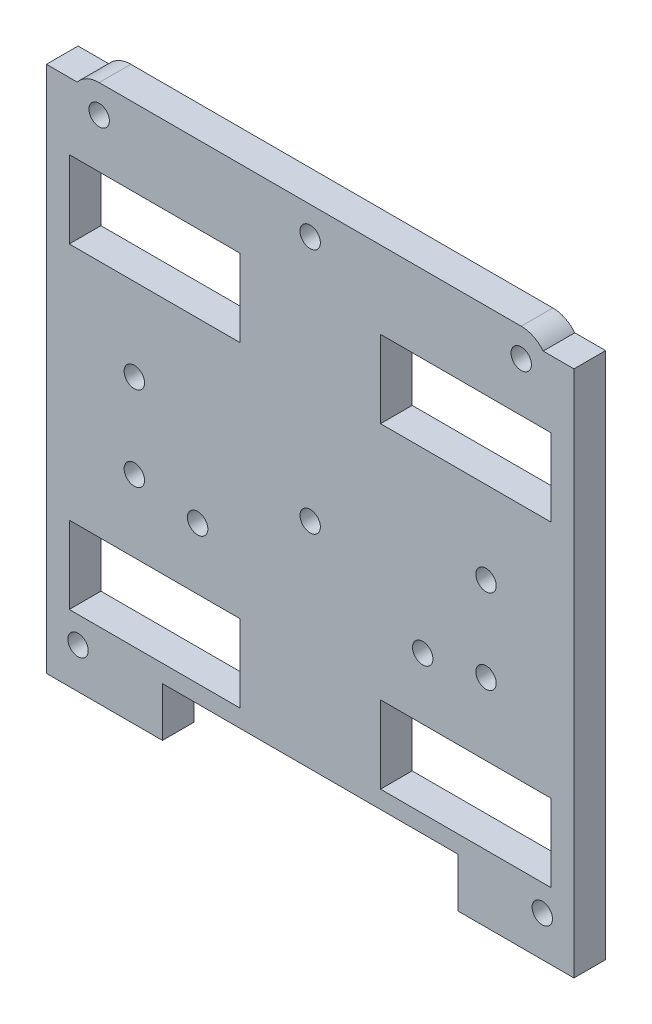
SolidWorks part; units mm, degrees
ref_plane "Front Plane" through (0, 0, 0) normal (0, 0, 1) x (1, 0, 0)
ref_plane "Top Plane" through (0, 0, 0) normal (0, 1, 0) x (1, 0, 0)
ref_plane "Right Plane" through (0, 0, 0) normal (1, 0, 0) x (0, 0, -1)
sketch "Sketch1" plane through (0, 0, 0) normal (0, 0, 1) x (1, 0, 0)
  line L0 (0, -37.5) -> (0, 37.5) construction
  line L1 (-47.5, -37.5) -> (47.5, -37.5)
  line L2 (-47.5, -37.5) -> (-47.5, 37.5)
  line L3 (-47.5, 37.5) -> (47.5, 37.5)
  line L4 (47.5, -37.5) -> (47.5, 37.5)
  line L5 (-47.5, -37.5) -> (47.5, 37.5) construction
  line L6 (-47.5, 37.5) -> (47.5, -37.5) construction
  line L7 (-47.5, 0) -> (47.5, 0) construction
  line L8 (-47.5, 22.5) -> (47.5, 22.5) construction
  line L9 (34.25, 17) -> (10, 28) construction
  line L10 (-34.25, 28) -> (-10, 28)
  line L11 (-34.25, 28) -> (-34.25, 17)
  line L12 (-34.25, 17) -> (-10, 17)
  line L13 (-10, 28) -> (-10, 17)
  line L14 (-34.25, 28) -> (-10, 17) construction
  line L15 (-34.25, 17) -> (-10, 28) construction
  line L16 (34.25, 28) -> (10, 17) construction
  line L17 (10, 28) -> (10, 17)
  line L18 (34.25, 17) -> (10, 17)
  line L19 (34.25, 28) -> (34.25, 17)
  line L20 (34.25, 28) -> (10, 28)
  line L21 (34.25, -28) -> (10, -17) construction
  line L22 (-34.25, -17) -> (-10, -28) construction
  line L23 (-34.25, -28) -> (-10, -17) construction
  line L24 (34.25, -17) -> (10, -28) construction
  line L25 (34.25, -28) -> (10, -28)
  line L26 (34.25, -28) -> (34.25, -17)
  line L27 (34.25, -17) -> (10, -17)
  line L28 (10, -28) -> (10, -17)
  line L29 (-10, -28) -> (-10, -17)
  line L30 (-34.25, -17) -> (-10, -17)
  line L31 (-34.25, -28) -> (-34.25, -17)
  line L32 (-34.25, -28) -> (-10, -28)
  point P0 (0, 0)
  point P12 (-22.125, 22.5)
  point P21 (22.125, 22.5)
  point P30 (22.125, -22.5)
  point P31 (-22.125, -22.5)
  dimension "D1" = 95
  dimension "D2" = 75
  dimension "D3" = 22.5
  dimension "D4" = 24.25
  dimension "D5" = 11
  dimension "D6" = 10
extrude "Boss-Extrude1" add sketch "Sketch1" along normal blind 4.5
sketch "Sketch8" plane through (0, 0, 4.5) normal (0, 0, 1) x (1, 0, 0)
  line L0 (-47.5, 37.5) -> (-47.5, -37.5) construction
  line L1 (47.5, -37.5) -> (47.5, 37.5) construction
  circle A0 centre (-47.5, 29.5) radius 8
  circle A1 centre (47.5, 29.5) radius 8
  dimension "D1" = 16
extrude "Boss-Extrude2" [suppressed] add sketch "Sketch8" against normal through all
sketch "Sketch2" plane through (0, 0, 4.5) normal (0, 0, 1) x (1, 0, 0)
  line L0 (0, -37.5) -> (0, 37.5) construction
  line L1 (-47.5, -37.5) -> (47.5, -37.5) construction
  line L2 (47.5, 37.5) -> (-47.5, 37.5) construction
  line L3 (-47.5, 0) -> (47.5, 0) construction
  line L4 (-47.5, 37.5) -> (-47.5, -37.5) construction
  line L5 (47.5, -37.5) -> (47.5, 37.5) construction
  line L6 (-40, 0) -> (40, 0) construction
  line L7 (-30, 35) -> (30, 35) construction
  circle A0 centre (-30, 35) radius 1.45
  circle A1 centre (30, 35) radius 1.45
  circle A2 centre (40, 0) radius 1.45
  circle A3 centre (-40, 0) radius 1.45
  circle A4 centre (0, 35) radius 1.45
  dimension "D1" = 2.9
  dimension "D7" = 2.9
  dimension "D8" = 2.9
  dimension "D9" = 2.9
  dimension "D2" = 30
  dimension "D3" = 35
  dimension "D4" = 80
  dimension "D5" = 40
  dimension "D6" = 0
extrude "screwHoles" cut sketch "Sketch2" against normal through all
sketch "Sketch3" plane through (0, 0, 4.5) normal (0, 0, 1) x (1, 0, 0)
  line L0 (-47.5, -20) -> (26.0486, -20) construction
  line L1 (-47.5, 37.5) -> (-47.5, -37.5) construction
  line L3 (0, 37.5) -> (0, -37.5) construction
  line L4 (47.5, 37.5) -> (-47.5, 37.5) construction
  line L5 (-47.5, -37.5) -> (47.5, -37.5) construction
  line L6 (18.95, -22.2) -> (9.05, -17.8) construction
  line L7 (-18.95, -17.8) -> (-9.05, -17.8)
  line L8 (-18.95, -17.8) -> (-18.95, -22.2)
  line L9 (-18.95, -22.2) -> (-9.05, -22.2)
  line L10 (-9.05, -17.8) -> (-9.05, -22.2)
  line L11 (-18.95, -17.8) -> (-9.05, -22.2) construction
  line L12 (-18.95, -22.2) -> (-9.05, -17.8) construction
  line L13 (18.95, -17.8) -> (9.05, -22.2) construction
  line L14 (9.05, -17.8) -> (9.05, -22.2)
  line L15 (18.95, -22.2) -> (9.05, -22.2)
  line L16 (18.95, -17.8) -> (18.95, -22.2)
  line L17 (18.95, -17.8) -> (9.05, -17.8)
  line L18 (-47.5, 37.5) -> (-47.5, -37.5) construction
  point P2 (-47.5, 0)
  point P12 (-14, -20)
  point P21 (14, -20)
  dimension "D1" = 9.9
  dimension "D3" = 14
  dimension "D4" = 20
extrude "BeltClamp" [suppressed] cut sketch "Sketch3" against normal through all
sketch "Sketch4" plane through (0, 0, 4.5) normal (0, 0, 1) x (1, 0, 0)
  line L0 (-47.5, 0) -> (47.5, 0) construction
  line L1 (-47.5, 37.5) -> (-47.5, -37.5) construction
  line L2 (47.5, -37.5) -> (47.5, 37.5) construction
  line L3 (0, 0) -> (0, 33.55) construction
  line L4 (-29.85, 2.175) -> (-20.15, 2.175)
  line L5 (-29.85, 2.175) -> (-29.85, -2.175)
  line L6 (-29.85, -2.175) -> (-20.15, -2.175)
  line L7 (-20.15, 2.175) -> (-20.15, -2.175)
  line L8 (-29.85, 2.175) -> (-20.15, -2.175) construction
  line L9 (-29.85, -2.175) -> (-20.15, 2.175) construction
  line L10 (29.85, -2.175) -> (20.15, 2.175) construction
  line L11 (29.85, 2.175) -> (20.15, -2.175) construction
  line L12 (20.15, 2.175) -> (20.15, -2.175)
  line L13 (29.85, -2.175) -> (20.15, -2.175)
  line L14 (29.85, 2.175) -> (29.85, -2.175)
  line L15 (29.85, 2.175) -> (20.15, 2.175)
  line L16 (-29.85, -2.175) -> (-20.15, 2.175) construction
  circle A0 centre (-40, 0) radius 1.45 construction
  circle A1 centre (0, 35) radius 1.45 construction
  circle A2 centre (0, 0) radius 1.45
  point P6 (-25, 0)
  point P22 (25, 0)
  dimension "D5" = 2.9
  dimension "D3" = 0
  dimension "D2" = 4.35
  dimension "D4" = 25
extrude "Cut-Extrude3" cut sketch "Sketch4" against normal through all
sketch "Sketch5" plane through (0, 0, 4.5) normal (0, 0, 1) x (1, 0, 0)
  line L0 (-47.5, -9.75) -> (47.5, -9.75) construction
  line L1 (-47.5, 37.5) -> (-47.5, -37.5) construction
  line L2 (47.5, -37.5) -> (47.5, 37.5) construction
  line L4 (0, -37.5) -> (0, 37.5) construction
  line L5 (-47.5, -37.5) -> (47.5, -37.5) construction
  line L6 (47.5, 37.5) -> (-47.5, 37.5) construction
  line L7 (-30.825, -14.6) -> (-35.175, -4.9) construction
  line L8 (30.825, -4.9) -> (35.175, -4.9)
  line L9 (30.825, -4.9) -> (30.825, -14.6)
  line L10 (30.825, -14.6) -> (35.175, -14.6)
  line L11 (35.175, -4.9) -> (35.175, -14.6)
  line L12 (30.825, -4.9) -> (35.175, -14.6) construction
  line L13 (30.825, -14.6) -> (35.175, -4.9) construction
  line L14 (-30.825, -4.9) -> (-35.175, -14.6) construction
  line L15 (-35.175, -4.9) -> (-35.175, -14.6)
  line L16 (-30.825, -14.6) -> (-35.175, -14.6)
  line L17 (-30.825, -4.9) -> (-30.825, -14.6)
  line L18 (-30.825, -4.9) -> (-35.175, -4.9)
  line L19 (33, -9.75) -> (33, -37.5) construction
  line L20 (-33, -9.75) -> (-33, -37.5) construction
  line L21 (-33, -31.75) -> (33, -31.75) construction
  circle A0 centre (33, -31.75) radius 1.45
  circle A1 centre (-33, -31.75) radius 1.45
  point P15 (33, -9.75)
  point P24 (-33, -9.75)
  dimension "D5" = 2.9
  dimension "D2" = 9.7
  dimension "D3" = 4.35
  dimension "D4" = 33
  dimension "D6" = 22
  dimension "D1" = 9.75
extrude "Cut-Extrude4" cut sketch "Sketch5" against normal through all
sketch "Sketch9" plane through (0, 0, 4.5) normal (0, 0, 1) x (1, 0, 0)
  line L0 (47.5, 37.5) -> (-47.5, 37.5) construction
  line L1 (0, 37.5) -> (0, -37.5) construction
  line L2 (-47.5, -37.5) -> (47.5, -37.5) construction
  line L3 (50.5, 35) -> (45.5, 35) construction
  line L4 (-50.5, 35) -> (-45.5, 35) construction
  circle A0 centre (-30, 35) radius 4
  circle A1 centre (-30, 35) radius 1.45
  circle A2 centre (-30, 35) radius 1.45 construction
  circle A3 centre (30, 35) radius 1.45
  circle A4 centre (30, 35) radius 4
  point P17 (0, -37.5)
  dimension "D1" = 8
extrude "Boss-Extrude3" add sketch "Sketch9" against normal through all
sketch "Sketch10" plane through (0, 0, 4.5) normal (0, 0, 1) x (1, 0, 0)
  line L0 (-60, 37.5) -> (-37.5, 37.5)
  line L1 (-37.5, 37.5) -> (-37.5, -37.5)
  line L2 (-47.5, -37.5) -> (47.5, -37.5) construction
  line L3 (-37.5, -37.5) -> (-60, -37.5)
  line L4 (-60, -37.5) -> (-60, 37.5)
  line L5 (0, 37.5) -> (0, -37.5) construction
  line L6 (26.8775, 37.5) -> (-26.8775, 37.5) construction
  line L7 (60, -37.5) -> (60, 37.5)
  line L8 (37.5, -37.5) -> (60, -37.5)
  line L9 (37.5, 37.5) -> (37.5, -37.5)
  line L10 (60, 37.5) -> (37.5, 37.5)
  line L11 (-60, -37.5) -> (-60, 37.5)
  line L12 (-33.1225, 37.5) -> (-47.5, 37.5) construction
  line M3 (47.5, -37.5) -> (47.5, 37.5)
  line M7 (-47.5, 37.5) -> (-47.5, -37.5)
  line M8 (-47.5, -37.5) -> (47.5, -37.5)
  dimension "D3" = 0
  dimension "D1" = 75
  dimension "D2" = 60
extrude "Cut-Extrude5" cut sketch "Sketch10" against normal through all contours L1 L0 M7 M8 | L10 L9 M3 M8 region at (42.5, 0, 4.5) region at (-42.5, 0, 4.5)
sketch "Sketch11" plane through (0, 0, 4.5) normal (0, 0, 1) x (1, 0, 0)
  line L0 (-30, 39) -> (30, 39)
  line L1 (30, 39) -> (26.8775, 37.5)
  line L2 (26.8775, 37.5) -> (-26.8775, 37.5)
  line L3 (-26.8775, 37.5) -> (-30, 39)
  arc A0 (-26.8775, 37.5) -> (-33.1225, 37.5) centre (-30, 35) ccw construction
  arc A1 (33.1225, 37.5) -> (26.8775, 37.5) centre (30, 35) ccw construction
extrude "Boss-Extrude4" add sketch "Sketch11" against normal through all
sketch "Sketch12" plane through (0, 0, 4.5) normal (0, 0, 1) x (1, 0, 0)
  line L0 (-37.5, -8.25) -> (37.5, -8.25) construction
  line L1 (-37.5, 37.5) -> (-37.5, -37.5) construction
  line L2 (37.5, 37.5) -> (37.5, -37.5) construction
  line L3 (0, 0) -> (0, -37.5) construction
  line L4 (-37.5, -37.5) -> (37.5, -37.5) construction
  circle A0 centre (-16, -8.25) radius 1.45
  circle A1 centre (16, -8.25) radius 1.45
  dimension "D2" = 2.9
  dimension "D1" = 16
  dimension "D3" = 8.25
extrude "FanBraceScrews" cut sketch "Sketch12" against normal through all
sketch "Sketch13" plane through (0, 0, 4.5) normal (0, 0, 1) x (1, 0, 0)
  line L0 (-37.5, -37.5) -> (37.5, -37.5) construction
  line L1 (-21, -44.5) -> (21, -44.5)
  line L2 (-21, -44.5) -> (-21, -30.5)
  line L3 (-21, -30.5) -> (21, -30.5)
  line L4 (21, -44.5) -> (21, -30.5)
  line L5 (-21, -44.5) -> (21, -30.5) construction
  line L6 (-21, -30.5) -> (21, -44.5) construction
  point P0 (0, -37.5)
  dimension "D1" = 42
  dimension "D2" = 7
extrude "Cut-Extrude7" cut sketch "Sketch13" against normal through all
sketch "Sketch14" plane through (0, 0, 4.5) normal (0, 0, 1) x (1, 0, 0)
  line L0 (16, -9.7) -> (16, 3.75) construction
  line L1 (0, 0) -> (0, -40.3958) construction
  line L2 (-16, -9.7) -> (-16, 3.75) construction
  circle A0 centre (16, -8.25) radius 1.45 construction
  circle A1 centre (16, 3.75) radius 1.45
  circle A2 centre (-16, 3.75) radius 1.45
  dimension "D2" = 2.9
  dimension "D1" = 12
extrude "Cut-Extrude8" [suppressed] cut sketch "Sketch14" against normal through all
sketch "Sketch15" plane through (0, 0, 4.5) normal (0, 0, 1) x (1, 0, 0)
  line L0 (-25, 5.25) -> (-25, -6.75) construction
  line L2 (0, 0) -> (0, -11.0705) construction
  line L3 (16, -8.3509) -> (25, -6.75) construction
  line L4 (25, 5.25) -> (25, -6.75) construction
  circle A0 centre (-25, 5.25) radius 1.45
  circle A1 centre (-25, -6.75) radius 1.45
  circle A2 centre (25, -6.75) radius 1.45
  circle A3 centre (25, 5.25) radius 1.45
  circle A5 centre (-16, -8.25) radius 1.45 construction
  dimension "D1" = 12
  dimension "D3" = 2.9
  dimension "D4" = 2.9
  dimension "D2" = 25
  dimension "D5" = 1.5
extrude "BeltClipScrews" cut sketch "Sketch15" against normal through all
sketch "Sketch16" plane through (0, 0, 4.5) normal (0, 0, 1) x (1, 0, 0)
  line L0 (0, 0) -> (0, -11.3016) construction
  line L1 (-29.85, 2.175) -> (-20.15, 2.175)
  line L2 (-29.85, 2.175) -> (-29.85, -2.175)
  line L3 (-29.85, -2.175) -> (-20.15, -2.175)
  line L4 (-20.15, 2.175) -> (-20.15, -2.175)
  line L5 (-35.175, -4.9) -> (-30.825, -4.9)
  line L6 (-35.175, -4.9) -> (-35.175, -14.6)
  line L7 (-35.175, -14.6) -> (-30.825, -14.6)
  line L8 (-30.825, -4.9) -> (-30.825, -14.6)
  line L9 (30.825, -4.9) -> (30.825, -14.6)
  line L10 (35.175, -14.6) -> (30.825, -14.6)
  line L11 (35.175, -4.9) -> (35.175, -14.6)
  line L12 (35.175, -4.9) -> (30.825, -4.9)
  line L13 (20.15, 2.175) -> (20.15, -2.175)
  line L14 (29.85, -2.175) -> (20.15, -2.175)
  line L15 (29.85, 2.175) -> (29.85, -2.175)
  line L16 (29.85, 2.175) -> (20.15, 2.175)
  line L17 (-30.825, -4.9) -> (-30.825, -14.6)
extrude "Boss-Extrude5" add sketch "Sketch16" against normal through all contours L8 L5 L6 L7 | L4 L1 L2 L3 | L15 L16 L13 L14 | L11 L12 L9 L10 region at (-25, 0, 4.5) region at (-33, -9.75, 4.5) region at (33, -9.75, 4.5) region at (25, 0, 4.5)
equation "\"X-ROD-SPACING\"=45"
equation "\"Y-ROD-SPACING\"=75"
equation "\"Z-ROD-SPACING\"=17.5"
equation "\"Y-BED-OFFSET\"=2"
equation "\"Y-BED-ROD-INSET\"=3.5"
equation "\"Y-BED-SCREW-SPACING\"=209"
equation "\"Y-BED-SCREW-CUTOUT-SLOT-HEIGHT\"=2"
equation "\"T-SLOT-NUT-FILLET-RADIUS\"=0.5"
equation "\"T-SLOT-SCREW-SHAFT-RADIUS\"=1.55"
equation "\"T-SLOT-SCREW-SHAFT-CUTOUT-LENGTH\"=11"
equation "\"T-SLOT-NUT-DEPTH\"=3.5"
equation "\"T-SLOT-NUT-WIDTH\"=2.85"
equation "\"T-SLOT-NUT-END-DISTANCE\"=8"
equation "\"ACRYLIC-THICKNESS\"=10"
equation "\"ACRYLIC-THICKNESS2\"=4.5"
equation "\"ACRYLIC-TAB-CUTOUT-SIZE\"=\"ACRYLIC-THICKNESS\"+\"ACRYLIC-TAB-TOLERANCE\"*2"
equation "\"ACRYLIC-TAB-WIDTH\"=\"ACRYLIC-THICKNESS\""
equation "\"ACRYLIC-M3-HOLE\"=2.9"
equation "\"SMOOTHROD-CAP-SCREW-DISTANCE\"=20"
equation "\"FRAME-WIDTH-INNER\"=370"
equation "\"NEMA17-HOLE-SPACING\"=31"
equation "\"NEMA17-CENTRAL-CUTOUT\"=22.5"
equation "\"Z-BRACKET-REACH\"=55"
equation "\"Z-ROD-INSET\"=13.5"
equation "\"TOP-BRACKET-SPACING\"=40"
equation "\"SMOOTHROD-X-LENGTH\"=350"
equation "\"SMOOTHROD-Y-LENGTH\"=350"
equation "\"SMOOTHROD-Z-LENGTH\"=350"
equation "\"SMOOTHROD-TIGHTENING-HEADROOM\"=.25"
equation "\"LEADSCREW-Z-LENGTH\"=300"
equation "\"SCREW-LENGTH-FRAME\"=\"ACRYLIC-THICKNESS\" + 10"
equation "\"SCREW-LENGTH-MOTOR\"=\"ACRYLIC-THICKNESS\" + 5"
equation "\"SCREW-HEAD-RADIUS\"=6"
equation "\"PRINTED-X-SMOOTHROD-DIAMETER\"=8.8"
equation "\"PRINTED-X-SMOOTHROD-CUTOUT\"=10"
equation "\"PRINTED-X-BASE-HEIGHT\"=10"
equation "\"PRINTED-LM8UU-CUTOUT-SIZE\"=15.5"
equation "\"PRINTED-LM8UU-CUTOUT-LENGTH\"=24.5"
equation "\"PRINTED-X-IDLER-HEIGHT\"=16"
equation "\"PSU-MOUNTING-WIDTH\"=95"
equation "\"PSU-MOUNTING-HEIGHT\"=177"
equation "\"Y-BELT-TO-ROD-DISTANCE\"=20"
equation "\"SPOOL-HOLDER-ROD-SPACING\"=150"
equation "\"D3@Sketch1\"=\"X-ROD-SPACING\"/2"
equation "\"D4@Sketch1\"=\"ACRYLIC-X-CARRIAGE-LM8UU-CUTOUT-WIDTH\""
equation "\"D1@Boss-Extrude1\"=\"ACRYLIC-THICKNESS2\""
equation "\"D1@Sketch2\"=\"ACRYLIC-M3-HOLE\""
equation "\"D1@Sketch3\"=\"ACRYLIC-TAB-CUTOUT-SIZE\""
equation "\"D2@Sketch3\"=\"ACRYLIC-THICKNESS2\"+\"ACRYLIC-TAB-TOLERANCE\"*2"
equation "\"ACRYLIC-X-CARRIAGE-WIDTH\"=55"
equation "\"ACRYLIC-X-CARRIAGE-HEIGHT\"=75"
equation "\"D2@Sketch1\"=\"ACRYLIC-X-CARRIAGE-HEIGHT\""
equation "\"ACRYLIC-X-CARRIAGE-CENTER-TAB-SPACING\"=14"
equation "\"D3@Sketch3\"=\"ACRYLIC-X-CARRIAGE-CENTER-TAB-SPACING\""
equation "\"SCREW-LENGTH-EXTRUDER\"=28"
equation "\"ACRYLIC-X-CARRIAGE-SCREW-SPACING-X\"=15"
equation "\"ACRYLIC-X-CARRIAGE-SCREW-SPACING-Y\"=33"
equation "\"D1@Sketch4\"=\"ACRYLIC-TAB-WIDTH\"-\"KERF\"*4"
equation "\"D2@Sketch4\"=\"ACRYLIC-THICKNESS2\"-\"KERF\"*2"
equation "\"D2@Sketch5\"=\"ACRYLIC-TAB-WIDTH\"-\"KERF\"*4"
equation "\"D3@Sketch5\"=\"ACRYLIC-THICKNESS2\"-\"KERF\"*2"
equation "\"ACRYLIC-X-CARRIAGE-EXTRUDER-SHELF-DEPTH\"=\"ACRYLIC-X-CARRIAGE-EXTRUDER-OFFSET\" + 28"
equation "\"ACRYLIC-X-CARRIAGE-EXTRUDER-BRACE-SPACING\"=23"
equation "\"D4@Sketch5\"=\"ACRYLIC-X-CARRIAGE-DUAL-MOUNT-BRACE-WIDTH\""
equation "\"D1@Sketch5\"=\"ACRYLIC-THICKNESS2\"/2 + 7.5"
equation "\"D4@Sketch2\"=\"ACRYLIC-X-CARRIAGE-DUAL-MOUNT-SCREW-WIDTH\"*2"
equation "\"D5@Sketch2\"=\"ACRYLIC-X-CARRIAGE-DUAL-MOUNT-SCREW-WIDTH\""
equation "\"D7@Sketch2\"=\"ACRYLIC-M3-HOLE\""
equation "\"D8@Sketch2\"=\"ACRYLIC-M3-HOLE\""
equation "\"ACRYLIC-X-CARRIAGE-LM8UU-CUTOUT-WIDTH\"=24.25"
equation "\"ACRYLIC-TAB-TOLERANCE\"=-.05"
equation "\"ACRYLIC-X-CARRIAGE-EXTRUDER-OFFSET\"=26"
equation "\"ACRYLIC-X-CARRIAGE-EXTRUDER-ANGLE\"=90"
equation "\"ACRYLIC-X-CARRIAGE-EXTRUDER-BRACE-TAB-OFFSET\"=20"
equation "\"ACRYLIC-X-CARRIAGE-EXTRUDER-BRACE-HEIGHT\"=35"
equation "\"ACRYLIC-X-CARRIAGE-EXTRUDER-BRACE-SCREW-SPACING\"=22"
equation "\"D5@Sketch5\"=\"ACRYLIC-M3-HOLE\""
equation "\"ACRYLIC-X-CARRIAGE-DUAL-WIDTH-MULTIPLIER\"=1.65"
equation "\"ACRYLIC-X-CARRIAGE-DUAL-HOTEND-SPACING\"=42"
equation "\"ACRYLIC-X-CARRIAGE-DUAL-WIDTH\"=75"
equation "\"ACRYLIC-X-CARRIAGE-DUAL-HOTEND-SEPARATION\"=36"
equation "\"ACRYLIC-X-CARRIAGE-DUAL-MOUNT-PLATE-DEPTH\"=75"
equation "\"ACRYLIC-X-CARRIAGE-DUAL-MOUNT-BRACE-WIDTH\"=33"
equation "\"ACRYLIC-X-CARRIAGE-DUAL-MOUNT-SCREW-WIDTH\"=40"
equation "\"D9@Sketch2\"=\"ACRYLIC-M3-HOLE\""
equation "\"ACRYLIC-X-CARRIAGE-LM8UU-CUTOUT-HEIGHT\"=11.0"
equation "\"D5@Sketch1\"=\"ACRYLIC-X-CARRIAGE-LM8UU-CUTOUT-HEIGHT\""
equation "\"D1@Sketch10\"=\"ACRYLIC-X-CARRIAGE-DUAL-WIDTH\""
equation "\"D5@Sketch4\"=\"ACRYLIC-M3-HOLE\""
equation "\"D2@Sketch12\"=\"ACRYLIC-M3-HOLE\""
equation "\"D3@Sketch12\"=\"ACRYLIC-THICKNESS2\"/2 + 6"
equation "\"D2@Sketch14\"=\"ACRYLIC-M3-HOLE\""
equation "\"D3@Sketch15\"=\"ACRYLIC-M3-HOLE\""
equation "\"D4@Sketch15\"=\"ACRYLIC-M3-HOLE\""
equation "\"KERF\"=0.075"
equation "\"ACRYLIC-THICKNESS-TAB-CUTOUT-WIDTH\"=\"ACRYLIC-THICKNESS\"-\"KERF\"*2"
equation "\"ACRYLIC-THICKNESS-TAB-CUTOUT-HEIGHT\"=\"ACRYLIC-TAB-WIDTH\"-\"KERF\"*4"
equation "\"ACRYLIC-THICKNESS2-TAB-CUTOUT-WIDTH\"=\"ACRYLIC-THICKNESS2\"-\"KERF\"*2"
equation "\"ACRYLIC-THICKNESS2-TAB-CUTOUT-HEIGHT\"=\"ACRYLIC-TAB-WIDTH\"-\"KERF\"*4"
equation "\"PRINTED-M3-HOLE\"=3.5"
equation "\"PRINTED-M3-NUT-AF\"=6.25"
equation "\"ACRYLIC-X-CARRIAGE-DUAL-FAN-OFFSET\"=52"
equation "\"ACRYLIC-X-CARRIAGE-DUAL-FAN-HEIGHT\"=20"
equation "\"BLOWER-FAN-WIDTH\"=15"
